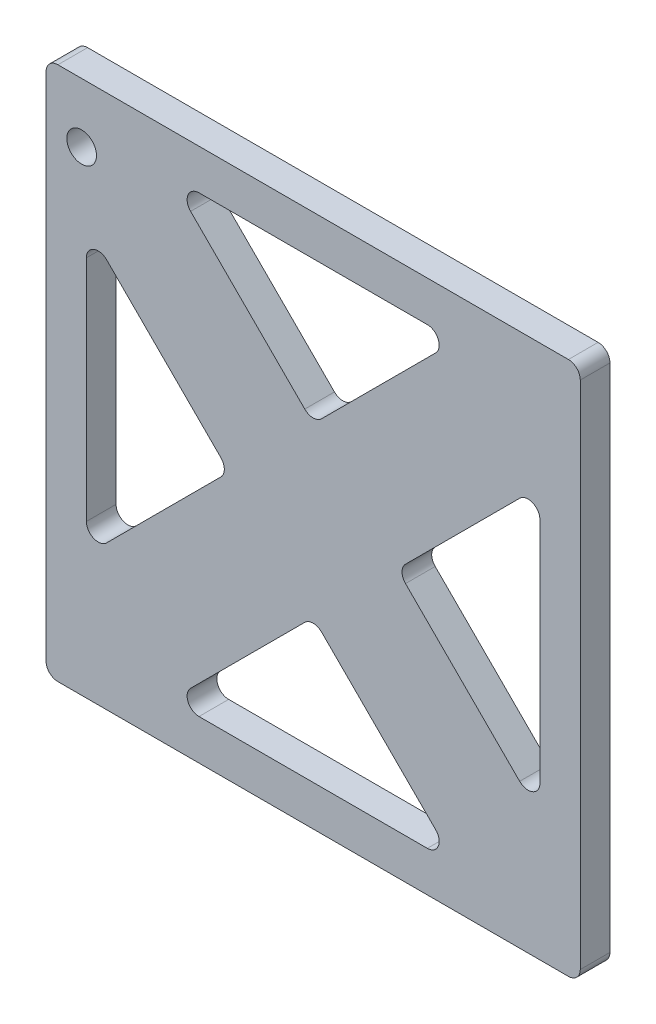
SolidWorks part; units mm, degrees
ref_plane "Front Plane" through (0, 0, 0) normal (0, 0, 1) x (1, 0, 0)
ref_plane "Top Plane" through (0, 0, 0) normal (0, 1, 0) x (1, 0, 0)
ref_plane "Right Plane" through (0, 0, 0) normal (1, 0, 0) x (0, 0, -1)
sketch "Sketch1" plane through (0, 0, 0) normal (0, 0, 1) x (1, 0, 0)
  line L5 (-54.61, -57.15) -> (54.61, -57.15)
  line L6 (-57.15, -54.61) -> (-57.15, 54.61)
  line L7 (-54.61, 57.15) -> (54.61, 57.15)
  line L13 (57.15, -54.61) -> (57.15, 54.61)
  line L23 (-57.15, -57.15) -> (-48.5178, -48.5178) construction
  line L25 (-24.4252, -48.5178) -> (24.4252, -48.5178)
  line L26 (-48.5178, -24.4252) -> (-48.5178, 24.4252)
  line L28 (48.5178, -24.4252) -> (48.5178, 24.4252)
  line L32 (-44.1818, 26.2212) -> (-19.7566, 1.7961)
  line L36 (44.1818, 26.2212) -> (19.7566, 1.7961)
  line L37 (26.2212, 44.1818) -> (1.7961, 19.7566)
  line L38 (-26.2212, 44.1818) -> (-1.7961, 19.7566)
  line L39 (-24.4252, 48.5178) -> (24.4252, 48.5178)
  line L40 (-19.7566, -1.7961) -> (-44.1818, -26.2212)
  line L41 (48.5178, 48.5178) -> (57.15, 57.15) construction
  line L44 (-1.7961, -19.7566) -> (-26.2212, -44.1818)
  line L45 (48.5178, -48.5178) -> (57.15, -57.15) construction
  line L46 (1.7961, -19.7566) -> (26.2212, -44.1818)
  line L47 (19.7566, -1.7961) -> (44.1818, -26.2212)
  circle A27 centre (-49.53, 44.45) radius 3.175
  arc A28 (26.2212, 44.1818) -> (24.4252, 48.5178) centre (24.4252, 45.9778) ccw
  arc A29 (-26.2212, 44.1818) -> (-24.4252, 48.5178) centre (-24.4252, 45.9778) cw
  arc A30 (1.7961, 19.7566) -> (-1.7961, 19.7566) centre (0, 21.5526) cw
  arc A31 (44.1818, 26.2212) -> (48.5178, 24.4252) centre (45.9778, 24.4252) cw
  arc A32 (19.7566, 1.7961) -> (19.7566, -1.7961) centre (21.5526, 0) ccw
  arc A33 (44.1818, -26.2212) -> (48.5178, -24.4252) centre (45.9778, -24.4252) ccw
  arc A34 (24.4252, -48.5178) -> (26.2212, -44.1818) centre (24.4252, -45.9778) ccw
  arc A35 (-26.2212, -44.1818) -> (-24.4252, -48.5178) centre (-24.4252, -45.9778) ccw
  arc A36 (-1.7961, -19.7566) -> (1.7961, -19.7566) centre (0, -21.5526) cw
  arc A37 (-44.1818, -26.2212) -> (-48.5178, -24.4252) centre (-45.9778, -24.4252) cw
  arc A38 (-19.7566, -1.7961) -> (-19.7566, 1.7961) centre (-21.5526, 0) ccw
  arc A39 (-44.1818, 26.2212) -> (-48.5178, 24.4252) centre (-45.9778, 24.4252) ccw
  arc A40 (-54.61, -57.15) -> (-57.15, -54.61) centre (-54.61, -54.61) cw
  arc A41 (54.61, -57.15) -> (57.15, -54.61) centre (54.61, -54.61) ccw
  arc A42 (54.61, 57.15) -> (57.15, 54.61) centre (54.61, 54.61) cw
  arc A43 (-57.15, 54.61) -> (-54.61, 57.15) centre (-54.61, 54.61) cw
  point P0 (0, 0)
  point P8 (0, 0)
  point P9 (0, 0)
  point P18 (0, 0)
  point P37 (17.9605, 0)
  point P46 (0, -17.9605)
  dimension "D3" = 12.7
  dimension "D4" = 6.35
  dimension "D6" = 2.54
  dimension "D5" = 2.54
  dimension "D1" = 7.62
  dimension "D2" = 114.3
extrude "Boss-Extrude2" add sketch "Sketch1" along normal mid plane 6.35
